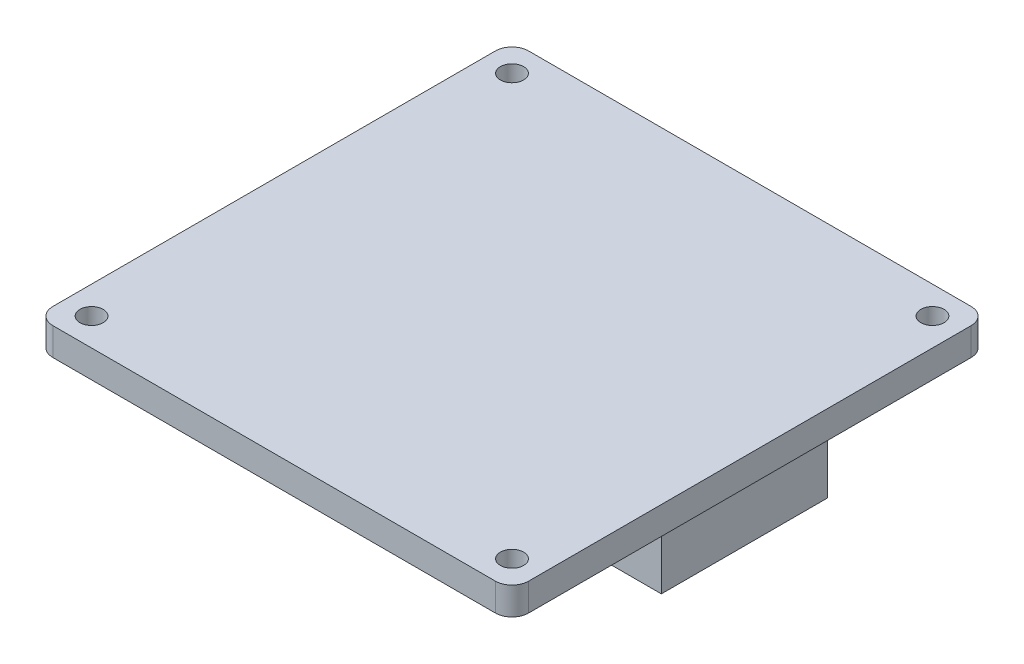
SolidWorks part; units mm, degrees
ref_plane "Спереди" through (0, 0, 0) normal (0, 0, 1) x (1, 0, 0)
ref_plane "Сверху" through (0, 0, 0) normal (0, 1, 0) x (1, 0, 0)
ref_plane "Справа" through (0, 0, 0) normal (1, 0, 0) x (0, 0, -1)
sketch "Эскиз1" plane through (0, 0, 0) normal (0, 1, 0) x (1, 0, 0)
  line L1 (-40.0001, 43.0001) -> (40.0001, 43.0001)
  line L2 (-43.0001, 40.0001) -> (-43.0001, -40.0001)
  line L3 (-40.0001, -43.0001) -> (40.0001, -43.0001)
  line L4 (43.0001, 40.0001) -> (43.0001, -40.0001)
  line L5 (-43.0001, 43.0001) -> (43.0001, -43.0001) construction
  line L6 (-43.0001, -43.0001) -> (43.0001, 43.0001) construction
  arc A0 (40.0001, -43.0001) -> (43.0001, -40.0001) centre (40.0001, -40.0001) ccw
  arc A1 (-43.0001, -40.0001) -> (-40.0001, -43.0001) centre (-40.0001, -40.0001) ccw
  arc A2 (-40.0001, 43.0001) -> (-43.0001, 40.0001) centre (-40.0001, 40.0001) ccw
  arc A3 (40.0001, 43.0001) -> (43.0001, 40.0001) centre (40.0001, 40.0001) cw
  circle A4 centre (-38, 38) radius 2.1
  circle A5 centre (38, 38) radius 2.1
  circle A6 centre (38, -38) radius 2.1
  circle A7 centre (-38, -38) radius 2.1
  point P0 (0, 0)
  dimension "D1" = 3
  dimension "D2" = 4
extrude "Бобышка-Вытянуть1" add sketch "Эскиз1" along normal blind 5
sketch "Эскиз2" plane through (0, 0, 0) normal (0, -1, 0) x (1, 0, 0)
  line L1 (-32, 5) -> (32, 5)
  line L2 (-32, 5) -> (-32, -25)
  line L3 (-32, -25) -> (32, -25)
  line L4 (32, 5) -> (32, -25)
  point P4 (0, 0)
  point P5 (0, 0)
  point P6 (0, 0)
extrude "Бобышка-Вытянуть2" add sketch "Эскиз2" along normal blind 20
